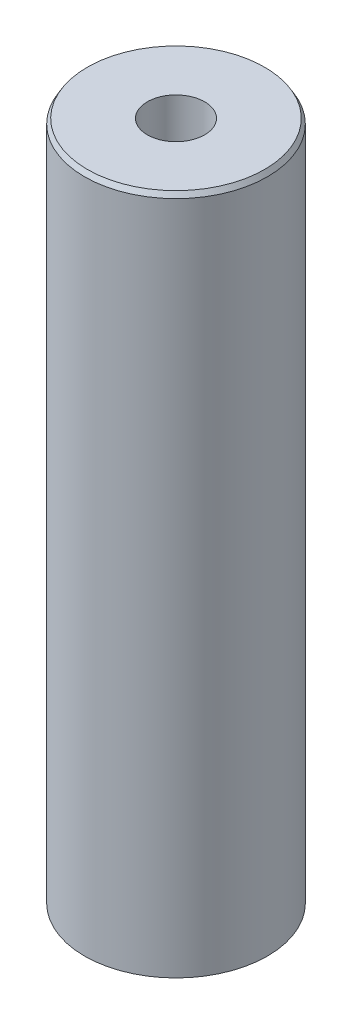
SolidWorks part; units mm, degrees
ref_plane "Front Plane" through (0, 0, 0) normal (0, 0, 1) x (1, 0, 0)
ref_plane "Top Plane" through (0, 0, 0) normal (0, 1, 0) x (1, 0, 0)
ref_plane "Right Plane" through (0, 0, 0) normal (1, 0, 0) x (0, 0, -1)
sketch "Sketch1" plane through (0, 0, 0) normal (0, 1, 0) x (1, 0, 0)
  circle A0 centre (0, 0) radius 15
  dimension "SHAFT_OD" = 30
extrude "Boss-Extrude1" add sketch "Sketch1" along normal blind 111.946
sketch "Sketch2" plane through (0, 0, 0) normal (0, 1, 0) x (1, 0, 0)
  circle A0 centre (0, 0) radius 4.7032
  dimension "BORE_D" = 9.4064
extrude "Cut-Extrude1" cut sketch "Sketch2" along normal through all
chamfer "Chamfer1" distance 0.8063 angle 30 2 edges at (0, 111.946, 15) (0, 0, 15) first distance on face at (0, 111.946, 15) first distance on face at (0, 0, 4.7032)
